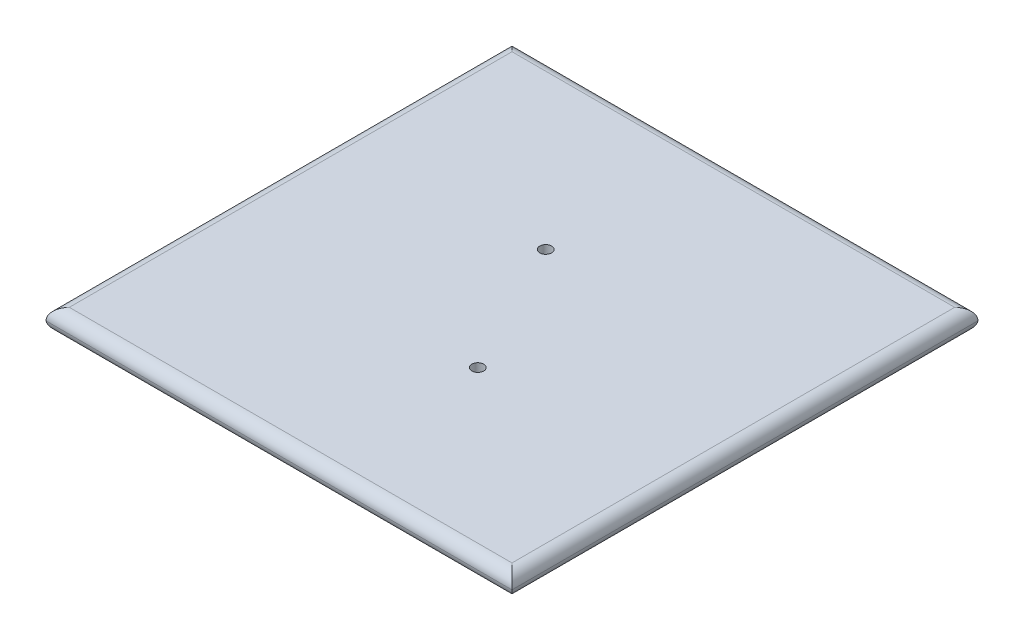
SolidWorks part; units mm, degrees
material "ABS"
ref_plane "Front Plane" through (0, 0, 0) normal (0, 0, 1) x (1, 0, 0)
ref_plane "Top Plane" through (0, 0, 0) normal (0, 1, 0) x (1, 0, 0)
ref_plane "Right Plane" through (0, 0, 0) normal (1, 0, 0) x (0, 0, -1)
sketch "Sketch1" plane through (0, 0, 0) normal (0, 1, 0) x (1, 0, 0)
  line L1 (-26.797, -23.495) -> (26.797, -23.495)
  line L2 (-26.797, -23.495) -> (-26.797, 23.495)
  line L3 (-26.797, 23.495) -> (26.797, 23.495)
  line L4 (26.797, -23.495) -> (26.797, 23.495)
  line L5 (-26.797, -23.495) -> (26.797, 23.495) construction
  line L6 (-26.797, 23.495) -> (26.797, -23.495) construction
  point P0 (0, 0)
  dimension "D1" = 46.99
  dimension "D2" = 53.594
extrude "Boss-Extrude1" add sketch "Sketch1" along normal blind 12.7
sketch "Sketch2" plane through (-26.797, 0, -3.302) normal (1, 0, 0) x (0, 0, -1)
  line L0 (-25.781, 0) -> (-21.7795, 8.5036)
  line L1 (-21.7795, 9.6538) -> (-21.7795, 8.5036)
  line L2 (15.1755, 9.6538) -> (-21.7795, 9.6538) construction
  line L3 (-3.302, 0) -> (-25.781, 0) construction
  line L4 (-3.302, 0) -> (-3.302, 9.6538) construction
  line L5 (-21.7795, 9.6538) -> (-26.797, 9.6538)
  line L7 (-26.797, 12.7) -> (-26.797, 0) construction
  line L8 (-26.797, 9.6538) -> (-26.797, 0)
  line L9 (-26.797, 0) -> (-25.781, 0)
  line L10 (19.177, 0) -> (20.193, 0)
  line L12 (20.193, 9.6538) -> (20.193, 0)
  line L13 (15.1755, 9.6538) -> (20.193, 9.6538)
  line L14 (15.1755, 9.6538) -> (15.1755, 8.5036)
  line L15 (19.177, 0) -> (15.1755, 8.5036)
  dimension "D1" = 9.398
  dimension "D3" = 22.479
  dimension "D4" = 64.8
extrude "Cut-Extrude1" cut sketch "Sketch2" along normal through all
sketch "Sketch3" plane through (0, 0, 23.495) normal (0, 0, 1) x (1, 0, 0)
  line L0 (0, 0) -> (-21.844, 0) construction
  line L1 (26.797, 0) -> (-26.797, 0) construction
  line L2 (-21.844, 0) -> (-21.844, 9.6538)
  line L4 (-21.844, 9.6538) -> (-26.797, 9.6538)
  line L5 (-26.797, 9.6538) -> (-26.797, 0)
  line L6 (-26.797, 0) -> (-21.844, 0)
  line L7 (0, 0) -> (0, 12.7) construction
  line L8 (-26.797, 12.7) -> (26.797, 12.7) construction
  line L9 (26.797, 0) -> (21.844, 0)
  line L10 (26.797, 9.6538) -> (26.797, 0)
  line L11 (21.844, 9.6538) -> (26.797, 9.6538)
  line L12 (21.844, 0) -> (21.844, 9.6538)
  line L13 (26.797, 9.6538) -> (-26.797, 9.6538) construction
  dimension "D1" = 21.844
extrude "Cut-Extrude2" cut sketch "Sketch3" against normal through all
sketch "Sketch4" plane through (0, 12.7, 0) normal (0, 1, 0) x (1, 0, 0)
  line L4 (26.797, -23.495) -> (26.797, 23.495)
  line L5 (26.797, 23.495) -> (-26.797, 23.495)
  line L6 (-26.797, 23.495) -> (-26.797, -23.495)
  line L7 (-26.797, -23.495) -> (26.797, -23.495)
  line L8 (26.797, -23.495) -> (26.797, 23.495)
  line L9 (26.797, 23.495) -> (-26.797, 23.495)
  line L10 (-26.797, 23.495) -> (-26.797, -23.495)
  line L11 (-26.797, -23.495) -> (26.797, -23.495)
  dimension "D1" = 0
extrude "Boss-Extrude2" add sketch "Sketch4" along normal blind 3.175
sketch "Sketch5" plane through (0, 15.875, 0) normal (0, 1, 0) x (1, 0, 0)
  line L1 (-50.8, -50.8) -> (50.8, -50.8)
  line L2 (-50.8, -50.8) -> (-50.8, 50.8)
  line L3 (-50.8, 50.8) -> (50.8, 50.8)
  line L4 (50.8, -50.8) -> (50.8, 50.8)
  line L5 (-50.8, -50.8) -> (50.8, 50.8) construction
  line L6 (-50.8, 50.8) -> (50.8, -50.8) construction
  point P0 (0, 0)
  dimension "D1" = 101.6
  dimension "D2" = 101.6
extrude "Boss-Extrude3" add sketch "Sketch5" along normal blind 4.7625
fillet "Fillet1" radius 7.62 4 edges at (-26.797, 15.875, 0) (0, 15.875, -23.495) (26.797, 15.875, 0) (0, 15.875, 23.495)
sketch "Sketch6" plane through (0, 0, 0) normal (0, -1, 0) x (1, 0, 0)
  line L0 (21.844, -18.4775) -> (21.844, 18.4775) construction
  line L1 (21.844, -18.4775) -> (-21.844, -18.4775) construction
  line L2 (21.844, 18.4775) -> (-21.844, 18.4775) construction
  line L3 (-21.844, -18.4775) -> (-21.844, 18.4775) construction
  line L4 (21.844, -18.4775) -> (21.844, 18.4775) construction
  line L5 (21.844, -18.4775) -> (-21.844, -18.4775) construction
  line L6 (21.844, 18.4775) -> (-21.844, 18.4775) construction
  line L7 (-21.844, -18.4775) -> (-21.844, 18.4775) construction
  line L8 (20.574, 17.2075) -> (-20.574, 17.2075)
  line L9 (-20.574, -17.2075) -> (-20.574, 17.2075)
  line L10 (20.574, -17.2075) -> (-20.574, -17.2075)
  line L11 (20.574, -17.2075) -> (20.574, 17.2075)
  line L12 (-20.574, 17.2075) -> (20.574, -17.2075) construction
  line L13 (20.574, 17.2075) -> (-20.574, -17.2075) construction
  dimension "D1" = 34.4151
  dimension "D2" = 36.9551
extrude "Cut-Extrude3" cut sketch "Sketch6" against normal up to surface (15.875 mm away) up to face at (0, 15.875, 0)
hole_wizard "Ø2.6 (2.6) Diameter Hole1" positions "Sketch8" profile "Sketch7" hole size "Ø2.6" standard "ANSI Metric" end condition through all
sketch "Sketch8" plane through (0, 20.6375, 0) normal (0, 1, 0) x (1, 0, 0)
  point P12 (-7.25, 14.6)
  point P14 (7.65, -15.1)
  dimension "D1" = 29.7
  dimension "D2" = 14.6
  dimension "D3" = 7.25
  dimension "D4" = 7.65
  dimension "D5" = 15.1
sketch "Sketch7" plane through (-7.25, 20.6375, -14.6) normal (1, 0, 0) x (0, 0, 1)
  line L0 (0, 0) -> (0, 20.6375)
  line L1 (0, 20.6375) -> (1.3, 20.6375)
  line L2 (1.3, 20.6375) -> (1.3, 0)
  line L5 (1.3, 0) -> (0, 0)
  line L11 (0, -6.35) -> (0, 107.95) construction
  dimension "Thru Hole Dia." = 2.6
  dimension "Thru Hole Depth" = 20.6375
fillet "Fillet2" radius 2.54 4 edges at (-50.8, 20.6375, 0) (0, 20.6375, -50.8) (50.8, 20.6375, 0) (0, 20.6375, 50.8)
fillet "Fillet3" radius 2.54 4 edges at (0, 15.875, -50.8) (-50.8, 15.875, 0) (50.8, 15.875, 0) (0, 15.875, 50.8)
fillet "Fillet4" radius 2.54 4 edges at (20.574, 7.9375, -17.2075) (-20.574, 7.9375, -17.2075) (-20.574, 7.9375, 17.2075) (20.574, 7.9375, 17.2075)
sketch "Sketch9" plane through (0, 0, 0) normal (0, -1, 0) x (1, 0, 0)
  line L0 (20.574, -14.6675) -> (20.574, 14.6675) construction
  line L1 (-20.574, -10.5578) -> (20.574, -10.5578)
  line L2 (-20.574, -10.5578) -> (-20.574, 10.5578)
  line L3 (-20.574, 10.5578) -> (20.574, 10.5578)
  line L4 (20.574, -10.5578) -> (20.574, 10.5578)
  line L5 (-20.574, -10.5578) -> (20.574, 10.5578) construction
  line L6 (-20.574, 10.5578) -> (20.574, -10.5578) construction
  point P0 (0, 0)
extrude "Boss-Extrude4" add sketch "Sketch9" against normal up to next contours L3 L4 L1 L2
fillet "Fillet5" radius 2.54 4 edges at (20.574, 7.9375, 10.5578) (-20.574, 7.9375, 10.5578) (20.574, 7.9375, -10.5578) (-20.574, 7.9375, -10.5578)
equation "\"D1@Sketch6\"=\"D2@Sketch6\"-.1"
